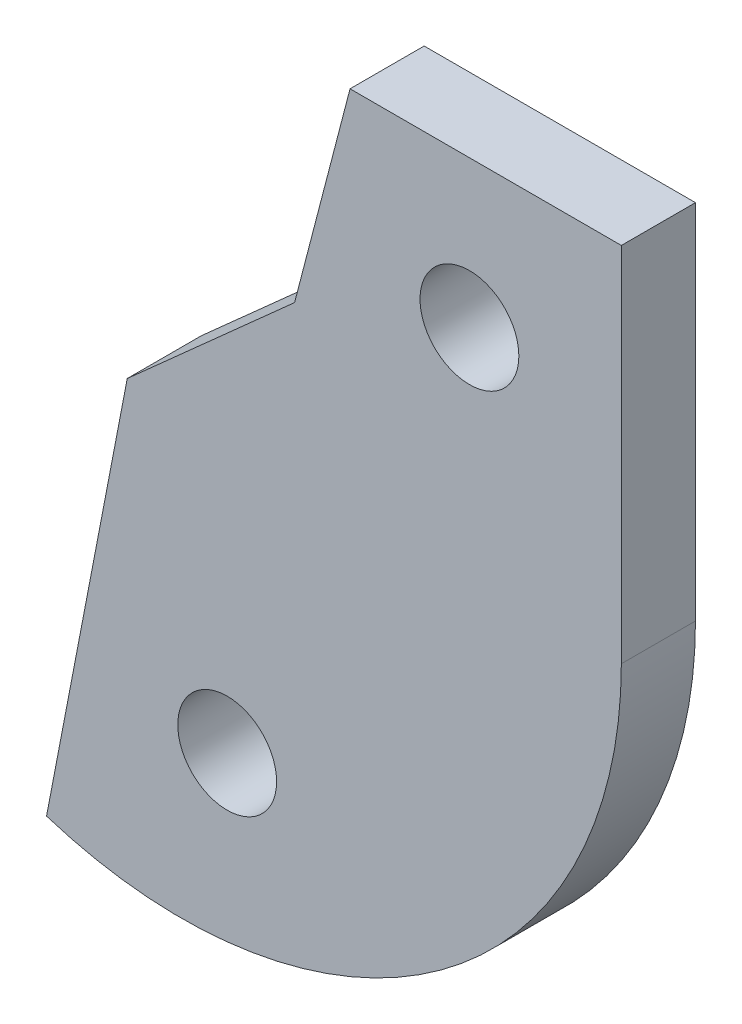
SolidWorks part; units mm, degrees
ref_plane "Płaszczyzna przednia" through (0, 0, 0) normal (0, 0, 1) x (1, 0, 0)
ref_plane "Płaszczyzna górna" through (0, 0, 0) normal (0, 1, 0) x (1, 0, 0)
ref_plane "Płaszczyzna prawa" through (0, 0, 0) normal (1, 0, 0) x (0, 0, -1)
sketch "Sketch2" plane through (0, 0, 0) normal (0, 0, 1) x (-1, 0, 0)
  line L0 (0, 7.3323) -> (-6.7742, 1.2836)
  line L1 (0, 7.3323) -> (-20, 7.3323)
  line L3 (-9.018, -7.3323) -> (-20, -7.3323)
  line L4 (-20, 7.3323) -> (-20, -7.3323)
  line L5 (3.2672, 24.3059) -> (0, 7.3323)
  line L6 (-6.7742, 1.2836) -> (-9.018, -7.3323)
  circle A2 centre (-13.851, -1.3792) radius 2
  arc A3 (-20, 7.3323) -> (3.2672, 24.3059) centre (-2.1752, 7.3323) cw
  circle A6 centre (-4.0453, 18.4434) radius 2
  dimension "D2" = 4
  dimension "D3" = 4
  dimension "D1" = 17.8248
  dimension "D4" = 14.6646
  dimension "D5" = 20
  dimension "D6" = 7.3323
extrude "Boss-Extrude1" add sketch "Sketch2" along normal blind 3 contours A3 L1 L5 A6 | L1 L4 L3 A2 region at (12.7061, -0.8811, 0) region at (7.8435, -15.3034, 0)
